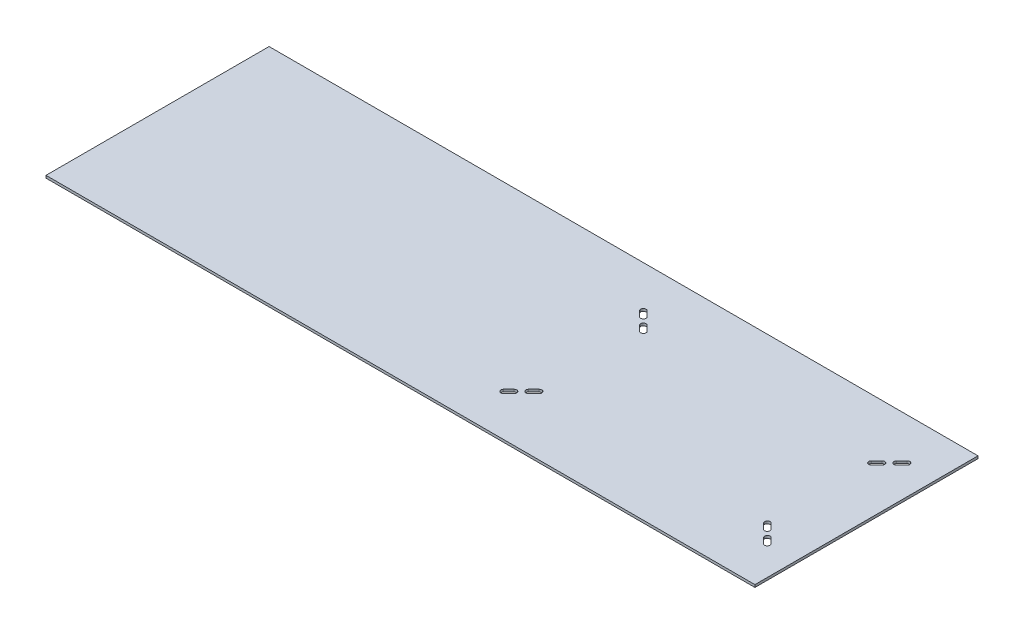
SolidWorks part; units mm, degrees
ref_plane "Front Plane" through (0, 0, 0) normal (0, 0, 1) x (1, 0, 0)
ref_plane "Top Plane" through (0, 0, 0) normal (0, 1, 0) x (1, 0, 0)
ref_plane "Right Plane" through (0, 0, 0) normal (1, 0, 0) x (0, 0, -1)
sketch "Sketch1" plane through (0, 0, 0) normal (0, 1, 0) x (1, 0, 0)
  line L1 (0, 0) -> (330.2, 0)
  line L2 (0, 0) -> (0, -228.6)
  line L3 (0, -228.6) -> (330.2, -228.6)
  line L4 (330.2, 0) -> (330.2, -228.6)
  dimension "D1" = 330.2
  dimension "D2" = 228.6
extrude "base plate" add sketch "Sketch1" against normal blind 2.54
sketch "center lines" plane through (0, 0, 0) normal (0, 1, 0) x (1, 0, 0)
  line L0 (165.1, 0) -> (165.1, -228.6) construction
  line L1 (330.2, 0) -> (0, 0) construction
  line L2 (0, -228.6) -> (330.2, -228.6) construction
  line L3 (0, -114.3) -> (330.2, -114.3) construction
  line L4 (0, 0) -> (0, -228.6) construction
  line L5 (330.2, -228.6) -> (330.2, 0) construction
sketch "Sketch3" plane through (0, 0, 0) normal (0, 1, 0) x (1, 0, 0)
  line L0 (21.0672, -185.8525) -> (30.0475, -194.8328)
  line L1 (30.0475, -194.8328) -> (60.5804, -164.2999)
  line L2 (60.5804, -164.2999) -> (51.6001, -155.3196)
  line L3 (51.6001, -155.3196) -> (21.0672, -185.8525)
  line L4 (29.9612, -185.9388) -> (35.3494, -180.5506) construction
  line L5 (28.0167, -183.9942) -> (33.4048, -178.6061)
  line L6 (31.9058, -187.8833) -> (37.2939, -182.4952)
  line L7 (0, -228.6) -> (330.2, -228.6) construction
  line L8 (48.2187, -167.6813) -> (42.8306, -173.0694) construction
  line L9 (50.1633, -169.6258) -> (44.7751, -175.014)
  line L10 (165.1, 0) -> (165.1, -228.6) construction
  line L11 (0, -114.3) -> (330.2, -114.3) construction
  line L12 (60.5804, -64.3001) -> (51.6001, -73.2804)
  line L13 (30.0475, -33.7672) -> (60.5804, -64.3001)
  line L14 (21.0672, -42.7475) -> (30.0475, -33.7672)
  line L15 (51.6001, -73.2804) -> (21.0672, -42.7475)
  line L16 (300.1525, -33.7672) -> (269.6196, -64.3001)
  line L17 (309.1328, -42.7475) -> (300.1525, -33.7672)
  line L18 (278.5999, -73.2804) -> (309.1328, -42.7475)
  line L19 (269.6196, -64.3001) -> (278.5999, -73.2804)
  line L20 (269.6196, -164.2999) -> (278.5999, -155.3196)
  line L21 (300.1525, -194.8328) -> (269.6196, -164.2999)
  line L22 (309.1328, -185.8525) -> (300.1525, -194.8328)
  line L23 (278.5999, -155.3196) -> (309.1328, -185.8525)
  line L24 (46.2742, -165.7367) -> (40.886, -171.1249)
  line L25 (29.9612, -42.6612) -> (35.3494, -48.0494) construction
  line L26 (28.0167, -44.6058) -> (33.4048, -49.9939)
  line L27 (31.9058, -40.7167) -> (37.2939, -46.1048)
  line L28 (48.2187, -60.9187) -> (42.8306, -55.5306) construction
  line L29 (50.1633, -58.9742) -> (44.7751, -53.586)
  line L30 (46.2742, -62.8633) -> (40.886, -57.4751)
  line L31 (300.2388, -42.6612) -> (294.8506, -48.0494) construction
  line L32 (302.1833, -44.6058) -> (296.7952, -49.9939)
  line L33 (298.2942, -40.7167) -> (292.9061, -46.1048)
  line L34 (281.9813, -60.9187) -> (287.3694, -55.5306) construction
  line L35 (280.0367, -58.9742) -> (285.4249, -53.586)
  line L36 (283.9258, -62.8633) -> (289.314, -57.4751)
  line L37 (281.9813, -167.6813) -> (287.3694, -173.0694) construction
  line L38 (280.0367, -169.6258) -> (285.4249, -175.014)
  line L39 (283.9258, -165.7367) -> (289.314, -171.1249)
  line L40 (300.2388, -185.9388) -> (294.8506, -180.5506) construction
  line L41 (302.1833, -183.9942) -> (296.7952, -178.6061)
  line L42 (298.2942, -187.8833) -> (292.9061, -182.4952)
  line L43 (51.6001, -164.2999) -> (51.6001, -155.3196)
  line L44 (60.5804, -164.2999) -> (51.6001, -164.2999)
  line L45 (51.6001, -64.3001) -> (51.6001, -73.2804)
  line L46 (60.5804, -64.3001) -> (51.6001, -64.3001)
  line L47 (278.5999, -64.3001) -> (278.5999, -73.2804)
  line L48 (269.6196, -64.3001) -> (278.5999, -64.3001)
  line L49 (278.5999, -164.2999) -> (278.5999, -155.3196)
  line L50 (269.6196, -164.2999) -> (278.5999, -164.2999)
  arc A0 (28.0167, -183.9942) -> (31.9058, -187.8833) centre (29.9612, -185.9388) ccw
  arc A1 (37.2939, -182.4952) -> (33.4048, -178.6061) centre (35.3494, -180.5506) ccw
  arc A2 (50.1633, -169.6258) -> (46.2742, -165.7367) centre (48.2187, -167.6813) ccw
  arc A3 (40.886, -171.1249) -> (44.7751, -175.014) centre (42.8306, -173.0694) ccw
  arc A4 (28.0167, -44.6058) -> (31.9058, -40.7167) centre (29.9612, -42.6612) cw
  arc A5 (37.2939, -46.1048) -> (33.4048, -49.9939) centre (35.3494, -48.0494) cw
  arc A6 (50.1633, -58.9742) -> (46.2742, -62.8633) centre (48.2187, -60.9187) cw
  arc A7 (40.886, -57.4751) -> (44.7751, -53.586) centre (42.8306, -55.5306) cw
  arc A8 (302.1833, -44.6058) -> (298.2942, -40.7167) centre (300.2388, -42.6612) ccw
  arc A9 (292.9061, -46.1048) -> (296.7952, -49.9939) centre (294.8506, -48.0494) ccw
  arc A10 (280.0367, -58.9742) -> (283.9258, -62.8633) centre (281.9813, -60.9187) ccw
  arc A11 (289.314, -57.4751) -> (285.4249, -53.586) centre (287.3694, -55.5306) ccw
  arc A12 (280.0367, -169.6258) -> (283.9258, -165.7367) centre (281.9813, -167.6813) cw
  arc A13 (289.314, -171.1249) -> (285.4249, -175.014) centre (287.3694, -173.0694) cw
  arc A14 (302.1833, -183.9942) -> (298.2942, -187.8833) centre (300.2388, -185.9388) cw
  arc A15 (292.9061, -182.4952) -> (296.7952, -178.6061) centre (294.8506, -180.5506) cw
  point P29 (32.6553, -183.2447)
  point P36 (45.5246, -170.3754)
  point P44 (32.6553, -45.3553)
  point P51 (45.5246, -58.2246)
  point P58 (297.5447, -45.3553)
  point P65 (284.6754, -58.2246)
  point P72 (284.6754, -170.3754)
  point P79 (297.5447, -183.2447)
  point P84 (37.2939, -178.6061)
  point P85 (40.886, -175.014)
  point P87 (49.3509, -158.496)
  dimension "D6" = 2.75
  dimension "D10" = 5.08
  dimension "D9" = 2.032
  dimension "D1" = 43.18
  dimension "D2" = 12.7
  dimension "D3" = 45
  dimension "D4" = 99.9998
  dimension "D5" = 226.9998
  dimension "D7" = 7.62
  dimension "D8" = 6.35
extrude "Cut-Extrude9" cut sketch "Sketch3" against normal through all contours A5 L27 A4 L26 | L33 A9 L32 A8 | L36 A11 L35 A10 | A13 L39 A12 L38 | A15 L42 A14 L41 | L6 A1 L5 A0 | L24 A3 L9 A2 | L30 A7 L29 A6 region at (32.6553, 0, 45.3553) region at (297.5447, 0, 45.3553) region at (284.6754, 0, 58.2246) region at (284.6754, 0, 170.3754) region at (297.5447, 0, 183.2447)
sketch "Sketch4" plane through (0, 0, 0) normal (0, 1, 0) x (1, 0, 0)
  line L0 (0, -228.6) -> (330.2, -228.6) construction
  line L1 (0, 0) -> (-396.24, 0)
  line L2 (0, 0) -> (0, -228.6)
  line L3 (0, -228.6) -> (-396.24, -228.6)
  line L4 (-396.24, 0) -> (-396.24, -228.6)
  dimension "D1" = 396.24
extrude "Boss-Extrude1" add sketch "Sketch4" against normal up to surface (2.54 mm away) up to face at (297.5447, -2.54, 183.2447)
